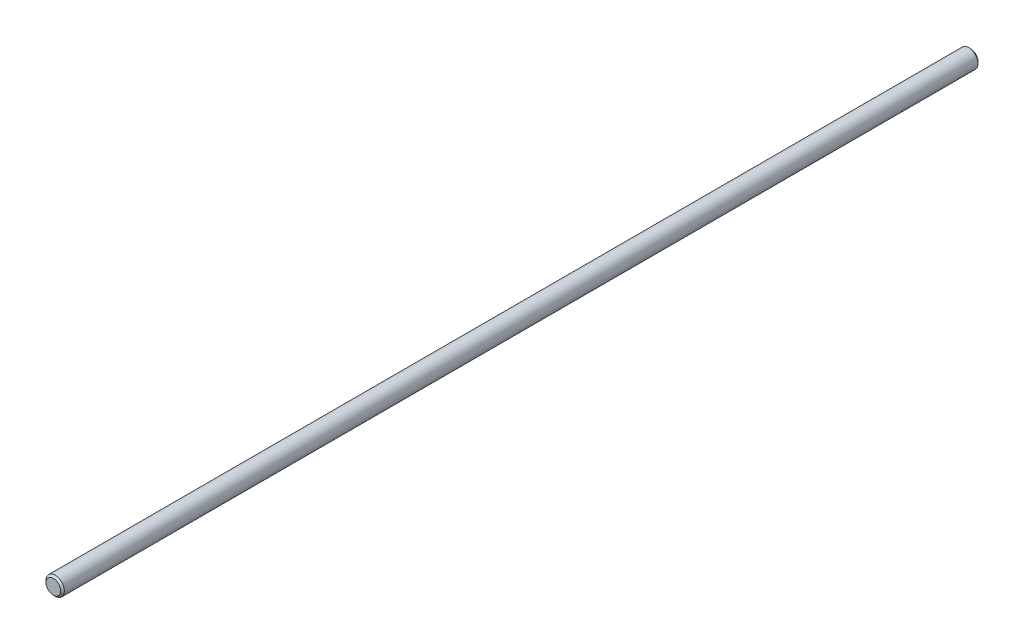
SolidWorks part; units mm, degrees
ref_plane "Plano frontal" through (0, 0, 0) normal (0, 0, 1) x (1, 0, 0)
ref_plane "Plano superior" through (0, 0, 0) normal (0, 1, 0) x (1, 0, 0)
ref_plane "Plano direito" through (0, 0, 0) normal (1, 0, 0) x (0, 0, -1)
sketch "Esboço1" plane through (0, 0, 0) normal (0, 0, 1) x (1, 0, 0)
  circle A0 centre (0, 0) radius 2.5
  dimension "D1" = 5
extrude "Ressalto-extrusão1" add sketch "Esboço1" along normal blind 250
chamfer "Chanfro1" distance 0.5 angle 45 2 edges at (2.5, 0, 0) (2.5, 0, 250)
